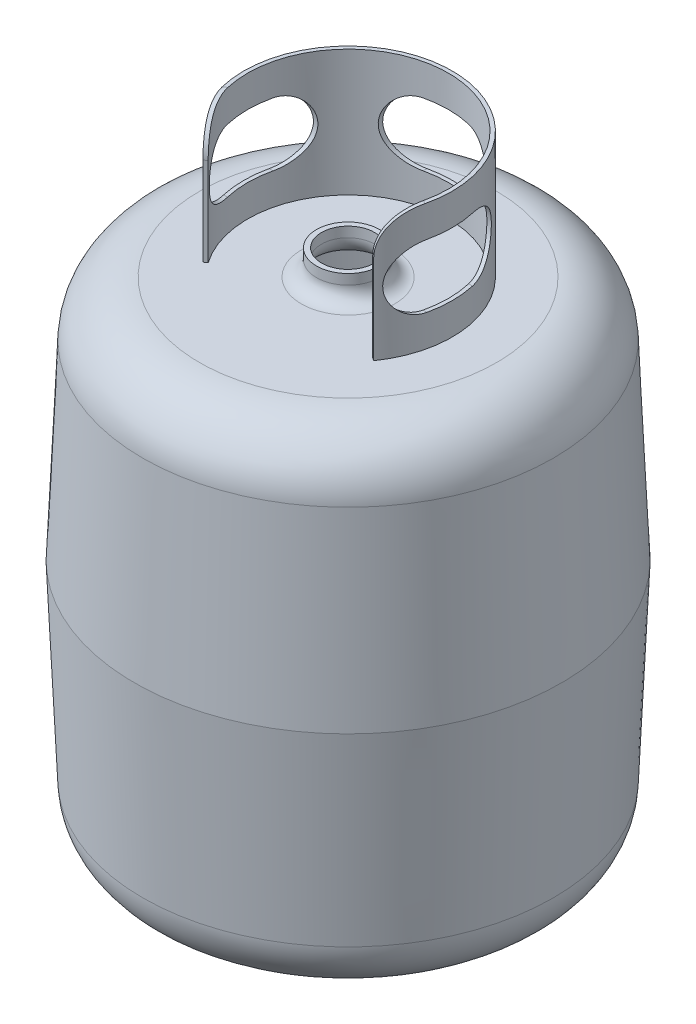
SolidWorks part; units mm, degrees
material "1060 Alloy"
ref_plane "Front Plane" through (0, 0, 0) normal (0, 0, 1) x (1, 0, 0)
ref_plane "Top Plane" through (0, 0, 0) normal (0, 1, 0) x (1, 0, 0)
ref_plane "Right Plane" through (0, 0, 0) normal (1, 0, 0) x (0, 0, -1)
sketch "Sketch1" plane through (0, 0, 0) normal (0, 0, 1) x (1, 0, 0)
  line L0 (0, 0) -> (50000, 0) construction
  line L1 (0, 0) -> (0, 50000) construction
  line L2 (0, -193.75) -> (-117.5428, -193.75)
  line L3 (-162.5, -150.7129) -> (-169.0803, 0)
  line L4 (-37, 193.75) -> (-117.5428, 193.75)
  line L5 (-162.5, 150.7129) -> (-169.0803, 0)
  line L6 (-25, 205.75) -> (-25, 213.75)
  line L7 (-21, 205.75) -> (-21, 213.75)
  line L8 (-37, 189.75) -> (-117.5428, 189.75)
  line L9 (-158.5038, 150.5384) -> (-165.0765, 0)
  line L10 (-158.5038, -150.5384) -> (-165.0765, 0)
  line L11 (0, -189.75) -> (-117.5428, -189.75)
  line L12 (-25, 213.75) -> (-21, 213.75)
  line L13 (0, -193.75) -> (0, -189.75)
  arc A0 (-162.5, -150.7129) -> (-117.5428, -193.75) centre (-117.5428, -148.75) ccw
  arc A1 (-162.5, 150.7129) -> (-117.5428, 193.75) centre (-117.5428, 148.75) cw
  arc A2 (-37, 193.75) -> (-25, 205.75) centre (-37, 205.75) ccw
  arc A3 (-37, 189.75) -> (-21, 205.75) centre (-37, 205.75) ccw
  arc A4 (-158.5038, 150.5384) -> (-117.5428, 189.75) centre (-117.5428, 148.75) cw
  arc A5 (-158.5038, -150.5384) -> (-117.5428, -189.75) centre (-117.5428, -148.75) ccw
  dimension "D4" = 90
  dimension "D7" = 12
  dimension "D1" = 92.5
  dimension "D2" = 325
  dimension "D3" = 387.5
  dimension "D5" = 50
  dimension "D6" = 20
  dimension "D8" = 4
revolve "Revolve1" add sketch "Sketch1" angle 360 about L1
sketch "Sketch4" plane through (0, -193.75, 0) normal (0, -1, 0) x (1, 0, 0)
  circle A0 centre (0, 0) radius 105.5428
  circle A1 centre (0, 0) radius 117.5428 construction
  circle A2 centre (0, 0) radius 117.5428
  circle A3 centre (0, 0) radius 102.5428
  dimension "D1" = 12
  dimension "D2" = 3
extrude "Boss-Extrude1" add sketch "Sketch4" along normal mid plane 30 contours A0 | A3
sketch "Sketch6" plane through (0, 193.75, 0) normal (0, 1, 0) x (1, 0, 0)
  line L0 (0, 0) -> (0, -117.5428) construction
  line L1 (0, 0) -> (-96.2854, -67.4198) construction
  line L2 (0, 0) -> (96.2854, -67.4198) construction
  line L3 (-67.578, -47.3186) -> (-65.1205, -45.5979)
  line L4 (65.1205, -45.5979) -> (67.578, -47.3186)
  circle A0 centre (0, 0) radius 117.5428 construction
  circle A1 centre (0, 0) radius 117.5428
  circle A2 centre (0, 0) radius 94.4975
  arc A3 (-67.578, -47.3186) -> (67.578, -47.3186) centre (0, 0) cw
  arc A4 (-65.1205, -45.5979) -> (65.1205, -45.5979) centre (0, 0) cw
  point P7 (48.1427, -33.7099)
  dimension "D2" = 23.0454
  dimension "D3" = 12
  dimension "D1" = 55
  dimension "D4" = 3
extrude "Boss-Extrude2" add sketch "Sketch6" along normal blind 100 contours A3 L4 A4 L3
fillet "Fillet1" radius 30 2 edges at (-66.3492, 293.75, 46.4582) (66.3492, 293.75, 46.4582)
sketch "Sketch7" plane through (0, 0, 0) normal (1, 0, 0) x (0, 0, -1)
  line L0 (0, -313.5397) -> (0, 313.5397) construction
  line L1 (-18, 243.75) -> (18, 243.75) construction
  line L2 (-18, 268.75) -> (18, 268.75)
  line L3 (-18, 218.75) -> (18, 218.75)
  line L4 (79.4975, 293.75) -> (-17.6519, 293.75) construction
  arc A0 (-18, 268.75) -> (-18, 218.75) centre (-18, 243.75) ccw
  arc A1 (18, 218.75) -> (18, 268.75) centre (18, 243.75) ccw
  point P4 (0, 0)
  point P7 (0, 243.75)
  dimension "D3" = 25
  dimension "D1" = 18
  dimension "D2" = 50
extrude "Cut-Extrude1" cut sketch "Sketch7" against normal mid plane 200
sketch "Sketch8" plane through (0, 0, 0) normal (0, 0, 1) x (1, 0, 0)
  line L0 (0, -310.2248) -> (0, 310.2248) construction
  line L1 (-18, 243.75) -> (18, 243.75) construction
  line L2 (-18, 268.75) -> (18, 268.75)
  line L3 (-18, 218.75) -> (18, 218.75)
  line L4 (79.4975, 293.75) -> (-79.4975, 293.75) construction
  arc A0 (-18, 268.75) -> (-18, 218.75) centre (-18, 243.75) ccw
  arc A1 (18, 218.75) -> (18, 268.75) centre (18, 243.75) ccw
  point P4 (0, 0)
  point P7 (0, 243.75)
  dimension "D3" = 25
  dimension "D1" = 18
  dimension "D2" = 50
extrude "Cut-Extrude2" cut sketch "Sketch8" against normal blind 200
equation "\"A\"= 325.00mm"
equation "\"B\"= 387.50mm"
